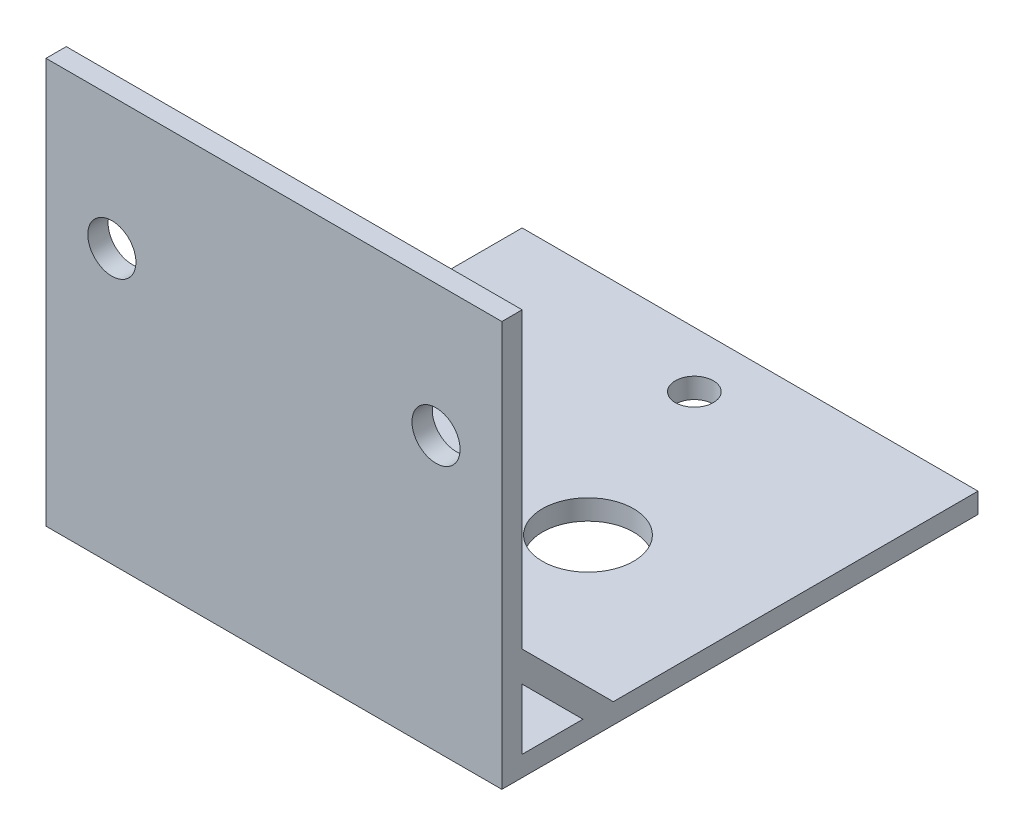
SolidWorks part; units mm, degrees
ref_plane "Front Plane" through (0, 0, 0) normal (0, 0, 1) x (1, 0, 0)
ref_plane "Top Plane" through (0, 0, 0) normal (0, 1, 0) x (1, 0, 0)
ref_plane "Right Plane" through (0, 0, 0) normal (1, 0, 0) x (0, 0, -1)
sketch "Sketch7" plane through (0, 0, 0) normal (0, 1, 0) x (1, 0, 0)
  line L0 (28.2563, -140.551) -> (-16.7437, -140.551)
  line L1 (28.2563, -95.551) -> (-16.7437, -95.551)
  line L2 (28.2563, -95.551) -> (28.2563, -142.551)
  line L3 (28.2563, -142.551) -> (-16.7437, -142.551)
  line L4 (-16.7437, -95.551) -> (-16.7437, -142.551)
  line L5 (28.2563, -95.551) -> (-16.7437, -142.551) construction
  line L6 (28.2563, -142.551) -> (-16.7437, -95.551) construction
  circle A0 centre (12.7563, -118.551) radius 4.5
  circle A1 centre (5.362, -118.9853) radius 14
  circle A2 centre (5.7563, -101.051) radius 1.875
  circle A3 centre (5.7563, -136.051) radius 1.875
  circle A4 centre (12.7563, -118.551) radius 3
  point P0 (5.7563, -119.051)
  dimension "D9" = 3.75
  dimension "D10" = 3.75
  dimension "D1" = 47
  dimension "D2" = 45
  dimension "D3" = 2
  dimension "D4" = 7
  dimension "D5" = 7
  dimension "D6" = 17.5
  dimension "D7" = 17.5
  dimension "D8" = 24
extrude "Boss-Extrude5" add sketch "Sketch7" along normal blind 2 separate body contours L1 L4 L0 L2 A3 A2 A1 | A1 A0 region at (5.7563, 0, 139.9146) region at (4.5101, 0, 119.0354)
extrude "Boss-Extrude6" add sketch "Sketch7<3>" along normal blind 40 contours L0 L4 L3 L2 region at (5.7563, 0, 141.551)
sketch "Sketch7<3>" plane through (0, 0, 0) normal (0, 1, 0) x (1, 0, 0) same geometry as "Sketch7"
sketch "Sketch8" plane through (-16.7437, 0, 0) normal (-1, 0, 0) x (0, 0, 1)
  line L0 (140.551, 8) -> (134.551, 2)
  line L1 (140.551, 40) -> (140.551, 2) construction
  line L2 (95.551, 2) -> (140.551, 2) construction
  line L3 (131.551, 2) -> (140.551, 11)
  line L4 (140.551, 11) -> (140.551, 8)
  line L5 (134.551, 2) -> (131.551, 2)
  dimension "D1" = 6
  dimension "D2" = 6
  dimension "D3" = 9
  dimension "D4" = 9
extrude "Boss-Extrude7" add sketch "Sketch8" against normal blind 2
ref_plane "Plane2" through (5.7563, 0, 0) normal (-1, 0, 0) x (0, 0, 1)
mirror "Mirror2" about plane through (5.7563, 0, 0) normal (-1, 0, 0) of "Boss-Extrude7"
sketch "Sketch9" plane through (0, 0, 142.551) normal (0, 0, 1) x (1, 0, 0)
  line L0 (5.7563, 22) -> (5.7563, -22) construction
  line L1 (-15.2437, 34) -> (26.7563, 34)
  line L2 (-15.2437, 34) -> (-15.2437, 20)
  line L3 (-15.2437, 20) -> (26.7563, 20)
  line L4 (26.7563, 34) -> (26.7563, 20)
  line L5 (-15.2437, 34) -> (26.7563, 20) construction
  line L6 (-15.2437, 20) -> (26.7563, 34) construction
  line L7 (28.2563, 0) -> (-16.7437, 0) construction
  point P0 (5.7563, 27)
  dimension "D1" = 20
  dimension "D2" = 14
  dimension "D3" = 42
sketch "Sketch10" plane through (0, 0, 142.551) normal (0, 0, 1) x (1, 0, 0)
  line L0 (26.7563, 34) -> (26.7563, 20) construction
  line L1 (-15.2437, 34) -> (26.7563, 34) construction
  line L2 (-15.2437, 34) -> (-15.2437, 20) construction
  circle A0 centre (21.7563, 27) radius 2.375
  circle A1 centre (-10.2437, 27) radius 2.375
  dimension "D1" = 5
  dimension "D2" = 4.75
  dimension "D4" = 4.75
  dimension "D3" = 7
  dimension "D5" = 7
  dimension "D6" = 5
extrude "Cut-Extrude2" cut sketch "Sketch10" against normal blind 5
